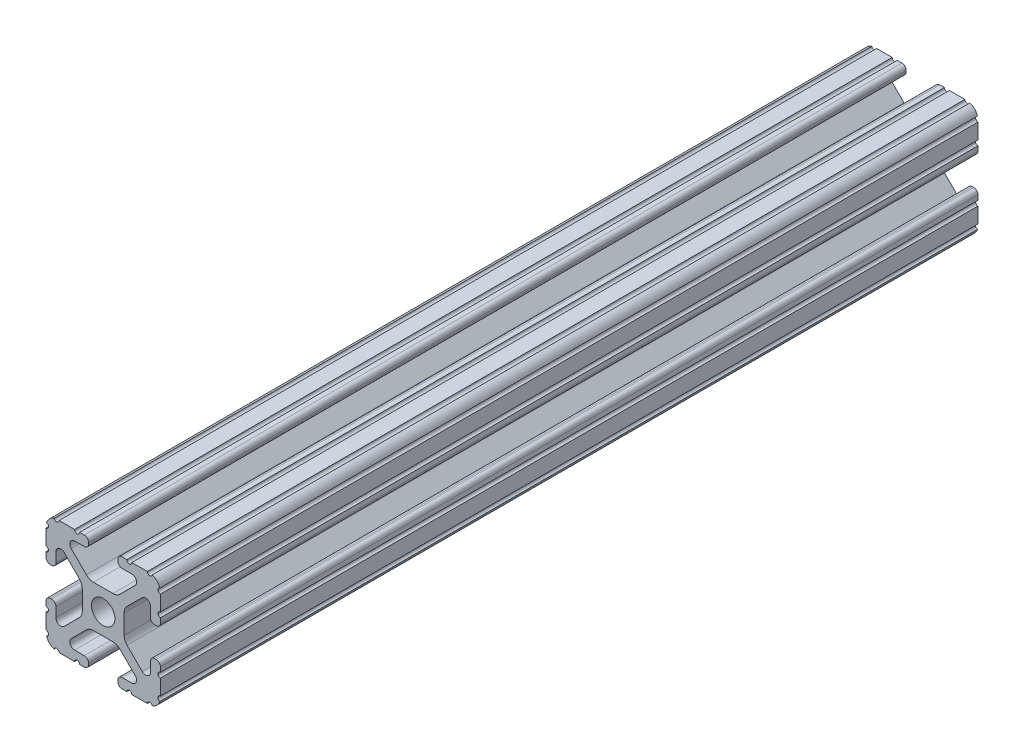
SolidWorks part; units mm, degrees
ref_plane "Front Plane" through (0, 0, 0) normal (0, 0, 1) x (1, 0, 0)
ref_plane "Top Plane" through (0, 0, 0) normal (0, 1, 0) x (1, 0, 0)
ref_plane "Right Plane" through (0, 0, 0) normal (1, 0, 0) x (0, 0, -1)
sketch "Sketch2" plane through (0, 0, 0) normal (0, 0, 1) x (1, 0, 0)
  line L0 (0, 12.7) -> (0, -12.7) construction
  line L1 (-12.7, 0) -> (12.7, 0) construction
  line L2 (3.2512, -12.7) -> (12.7, -12.7)
  line L3 (12.7, -12.7) -> (12.7, -3.2512)
  line L4 (3.2512, -12.7) -> (3.2512, -10.4902)
  line L5 (3.2512, -10.4902) -> (8.9276, -10.4902)
  line L6 (8.9276, -10.4902) -> (3.0856, -4.6482)
  line L7 (0, 0) -> (12.7, -12.7) construction
  line L8 (12.7, -3.2512) -> (10.4902, -3.2512)
  line L9 (10.4902, -3.2512) -> (10.4902, -8.9276)
  line L10 (10.4902, -8.9276) -> (4.6482, -3.0856)
  circle A0 centre (0, 0) radius 2.6035
  arc A1 (6.3485, -10.4902) -> (7.1039, -8.6665) centre (6.3485, -9.4219) ccw construction
  point P8 (0, -4.6482)
  dimension "Center Hole Diameter" = 5.207
  dimension "Rail Height" = 25.4
  dimension "Rail Width" = 25.4
  dimension "T-Slot Width" = 6.5024
  dimension "Slot Inner Width" = 14.8336
  dimension "Thickness" = 2.2098
  dimension "Slot Depth" = 5.842
  dimension "D1" = 2.2098
sketch "Sketch3" plane through (0, 0, 0) normal (1, 0, 0) x (0, 0, -1)
  line L0 (-90.7763, -12.7) -> (90.7763, -12.7) construction
  line L1 (-65.3763, 0) -> (65.3763, 0) construction
  line L2 (90.7763, 0) -> (-90.7763, 0) construction
sketch "Sketch4" plane through (0, 0, 0) normal (0, 0, 1) x (1, 0, 0)
  line L0 (4.1904, -12.7) -> (10.1173, -12.7)
  line L1 (3.2512, -12.7) -> (12.7, -12.7) construction
  line L2 (3.2512, -12.7) -> (3.2512, -10.4902) construction
  line L3 (3.2512, -10.4902) -> (8.9276, -10.4902) construction
  line L4 (3.2512, -11.4294) -> (3.2512, -11.7608)
  line L5 (4.1904, -10.4902) -> (6.3485, -10.4902)
  line L6 (0, -4.6482) -> (2.164, -4.6482)
  line L7 (8.9276, -10.4902) -> (3.0856, -4.6482) construction
  line L8 (3.7373, -5.2999) -> (7.1039, -8.6665)
  line L9 (12.7, -12.7) -> (12.7, -3.2512) construction
  line L10 (10.4902, -8.9276) -> (4.6482, -3.0856) construction
  line L11 (10.4902, -3.2512) -> (10.4902, -8.9276) construction
  line L12 (10.4902, -6.3485) -> (10.4902, -4.1904)
  line L13 (12.7, -3.2512) -> (10.4902, -3.2512) construction
  line L14 (11.4294, -3.2512) -> (11.7608, -3.2512)
  line L15 (12.7, -4.1904) -> (12.7, -10.1173)
  line L16 (8.6665, -7.1039) -> (5.2999, -3.7373)
  line L17 (4.6482, 0) -> (4.6482, -2.164)
  line L18 (-12.7, 0) -> (12.7, 0) construction
  line L19 (0, -4.6482) -> (0, -2.6035)
  line L20 (0, 12.7) -> (0, -12.7) construction
  line L21 (4.6482, 0) -> (2.6035, 0)
  arc A0 (3.2512, -11.7608) -> (4.1904, -12.7) centre (4.1904, -11.7608) ccw
  arc A2 (3.2512, -11.4294) -> (4.1904, -10.4902) centre (4.1904, -11.4294) cw
  arc A3 (6.3485, -10.4902) -> (7.1039, -8.6665) centre (6.3485, -9.4219) ccw
  arc A4 (2.164, -4.6482) -> (3.7373, -5.2999) centre (2.164, -6.8732) cw
  arc A5 (10.1173, -12.7) -> (12.7, -10.1173) centre (10.1173, -10.1173) ccw
  arc A6 (8.6665, -7.1039) -> (10.4902, -6.3485) centre (9.4219, -6.3485) ccw
  arc A7 (10.4902, -4.1904) -> (11.4294, -3.2512) centre (11.4294, -4.1904) cw
  arc A8 (11.7608, -3.2512) -> (12.7, -4.1904) centre (11.7608, -4.1904) cw
  arc A9 (5.2999, -3.7373) -> (4.6482, -2.164) centre (6.8732, -2.164) cw
  circle A10 centre (0, 0) radius 2.6035 construction
  arc A11 (0, -2.6035) -> (2.6035, 0) centre (0, 0) ccw
  dimension "D1" = 2.5827
  dimension "D2" = 2.225
  dimension "D3" = 0.9392
extrude "Boss-Extrude1" add sketch "Sketch4" along normal up to vertex (90.7763 mm away) from vertex up to point (0, -12.7, 90.7763) starting at point (0, -12.7, -90.7763)
sketch "Sketch5" plane through (0, 0, 0) normal (0, 0, 1) x (1, 0, 0)
  line L0 (3.2512, -12.7) -> (12.7, -12.7) construction
  line L1 (4.1904, -10.4902) -> (6.3485, -10.4902) construction
  line L3 (0, 0) -> (12.7, -12.7) construction
  line L4 (6.3485, -10.4902) -> (6.3485, -12.7) construction
  line L5 (8.9276, -10.4902) -> (3.0856, -4.6482) construction
  circle A0 centre (10.3562, -12.7) radius 0.5524
  circle A1 centre (5.796, -12.7) radius 0.5524
  circle A2 centre (12.7, -10.3562) radius 0.5524
  circle A3 centre (12.7, -5.796) radius 0.5524
  point P10 (5.2694, -10.4902)
  point P12 (9.4219, -6.3485)
  dimension "D1" = 1.1049
extrude "Cut-Extrude1" cut sketch "Sketch5" against normal through all both and the other way through all
mirror "Mirror1" about plane through (0, 0, 0) normal (1, 0, 0) of bodies 137 134
mirror "Mirror2" about plane through (0, 0, 0) normal (0, 1, 0) of bodies 135
equation "\"D1@Sketch2\"=\"Thickness@Sketch2\""
equation "\"D2@Sketch4\"=\"Slot Inner Width@Sketch2\"*0.15"
equation "\"D1@Sketch4\"=\"D3@Sketch4\"*2.75"
equation "\"D3@Sketch4\"=\"Thickness@Sketch2\"*0.425"
equation "\"D1@Sketch5\"=\"Thickness@Sketch2\"*0.5"
equation "\"D1@Boss-Extrude1\"=\"Length@Sketch3\""
